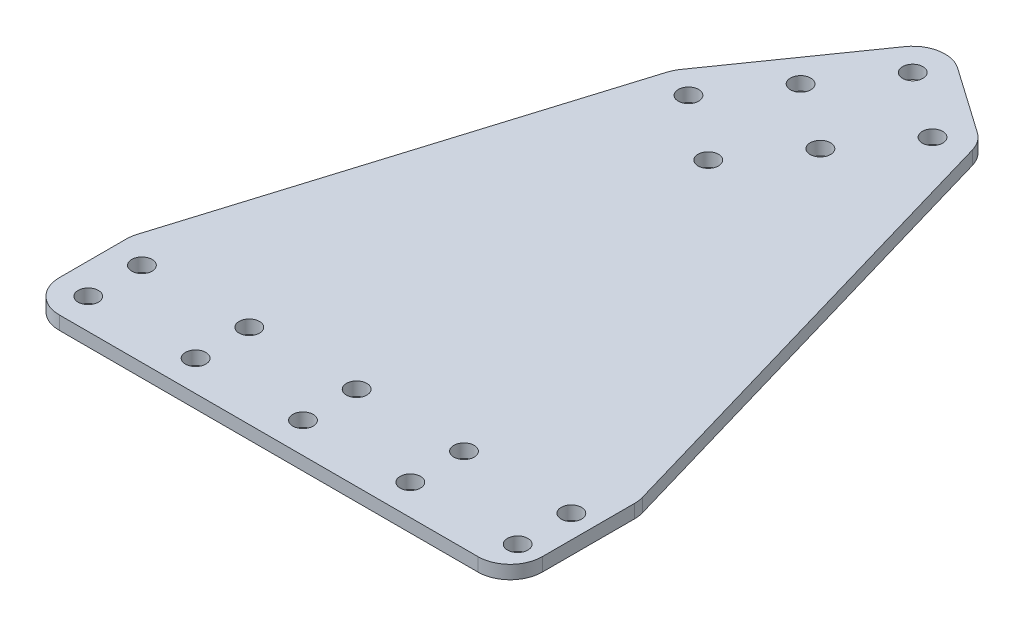
SolidWorks part; units mm, degrees
material "6061-T6 (SS)"
ref_plane "Front Plane" through (0, 0, 0) normal (0, 0, 1) x (1, 0, 0)
ref_plane "Top Plane" through (0, 0, 0) normal (0, 1, 0) x (1, 0, 0)
ref_plane "Right Plane" through (0, 0, 0) normal (1, 0, 0) x (0, 0, -1)
sketch "Sketch1" plane through (0, 0, 0) normal (0, 1, 0) x (1, 0, 0)
  line L5 (0, 0) -> (114.3, 0)
  line L6 (0, 0) -> (0, 181.61)
  line L7 (0, 181.61) -> (114.3, 181.61)
  line L8 (114.3, 0) -> (114.3, 181.61)
  dimension "D1" = 181.61
  dimension "D2" = 114.3
extrude "Boss-Extrude1" add sketch "Sketch1" along normal blind 3.175
sketch "Sketch2" plane through (0, 3.175, 0) normal (0, 1, 0) x (1, 0, 0)
  line L0 (0, 0) -> (114.3, 0) construction
  line L1 (0, 181.61) -> (0, 0) construction
  circle A0 centre (7.239, 7.239) radius 2.413
  circle A2 centre (7.239, 19.939) radius 2.413
  circle A3 centre (32.639, 19.939) radius 2.413
  circle A4 centre (58.039, 19.939) radius 2.413
  circle A5 centre (83.439, 19.939) radius 2.413
  circle A6 centre (108.839, 19.939) radius 2.413
  circle A7 centre (32.639, 7.239) radius 2.413
  circle A8 centre (58.039, 7.239) radius 2.413
  circle A9 centre (83.439, 7.239) radius 2.413
  circle A10 centre (108.839, 7.239) radius 2.413
  dimension "D1" = 4.826
  dimension "D2" = 7.239
  dimension "D3" = 7.239
  dimension "D4" = 2
  dimension "D5" = 5
extrude "Cut-Extrude1" cut sketch "Sketch2" against normal through all
sketch "Sketch3" plane through (0, 0, 0) normal (0, -1, 0) x (1, 0, 0)
  line L10 (37.07, -119.4115) -> (58.9233, -150.6212) construction
  line L11 (37.07, -119.4115) -> (52.6748, -108.4849) construction
  line L12 (58.9233, -150.6212) -> (74.5281, -139.6946) construction
  line L13 (52.6748, -108.4849) -> (74.5281, -139.6946) construction
  line L14 (0, -1.7463) -> (0, 1.7463) construction
  circle A14 centre (37.07, -119.4115) radius 2.413
  circle A15 centre (52.6748, -108.4849) radius 2.413
  circle A16 centre (74.5281, -139.6946) radius 2.413
  circle A17 centre (58.9233, -150.6212) radius 2.413
  circle A18 centre (47.9966, -135.0164) radius 2.413
  circle A19 centre (63.6015, -124.0897) radius 2.413
  dimension "D4" = 19.05
  dimension "D5" = 108.4849
  dimension "D2" = 4.826
  dimension "D1" = 35
  dimension "D6" = 52.6748
  dimension "D3" = 19.05
extrude "Cut-Extrude2" cut sketch "Sketch3" against normal through all
sketch "Sketch4" plane through (0, 0, 0) normal (0, -1, 0) x (1, 0, 0)
  line L0 (57.052, -161.2338) -> (30.1383, -122.7972)
  line L2 (114.3, -181.61) -> (0, -181.61)
  line L3 (0, -181.61) -> (0, -24.617)
  line L5 (114.3, -30.5457) -> (81.0932, -144.3999)
  line L6 (114.3, 0) -> (114.3, -181.61) construction
  line L7 (114.3, -30.5457) -> (114.3, -181.61)
  line L9 (37.07, -119.4115) -> (58.9233, -150.6212) construction
  line L10 (58.9233, -150.6212) -> (74.5281, -139.6946) construction
  line L11 (57.052, -161.2338) -> (81.0932, -144.3999)
  line L12 (30.1383, -122.7972) -> (0, -24.617)
  line L13 (0, -1.7463) -> (0, 1.7463) construction
  circle A0 centre (74.5281, -139.6946) radius 2.413 construction
  circle A1 centre (58.9233, -150.6212) radius 2.413 construction
  circle A2 centre (37.07, -119.4115) radius 2.413 construction
  circle A3 centre (74.5281, -139.6946) radius 2.413 construction
  circle A4 centre (58.9233, -150.6212) radius 2.413 construction
  circle A5 centre (37.07, -119.4115) radius 2.413 construction
  circle A6 centre (108.839, -19.939) radius 2.413 construction
  circle A7 centre (7.239, -19.939) radius 2.413 construction
  circle A8 centre (108.839, -19.939) radius 2.413 construction
  circle A9 centre (7.239, -19.939) radius 2.413 construction
  dimension "D1" = 7.62
  dimension "D2" = 7.62
  dimension "D3" = 7.62
  dimension "D4" = 7.62
extrude "Cut-Extrude3" cut sketch "Sketch4" against normal through all
fillet "Fillet1" radius 7.62 7 edges at (114.3, 1.5875, -30.5457) (0, 1.5875, -24.617) (30.1383, 1.5875, -122.7972) (57.052, 1.5875, -161.2338) (81.0932, 1.5875, -144.3999) (0, 1.5875, 0) (114.3, 1.5875, 0)
